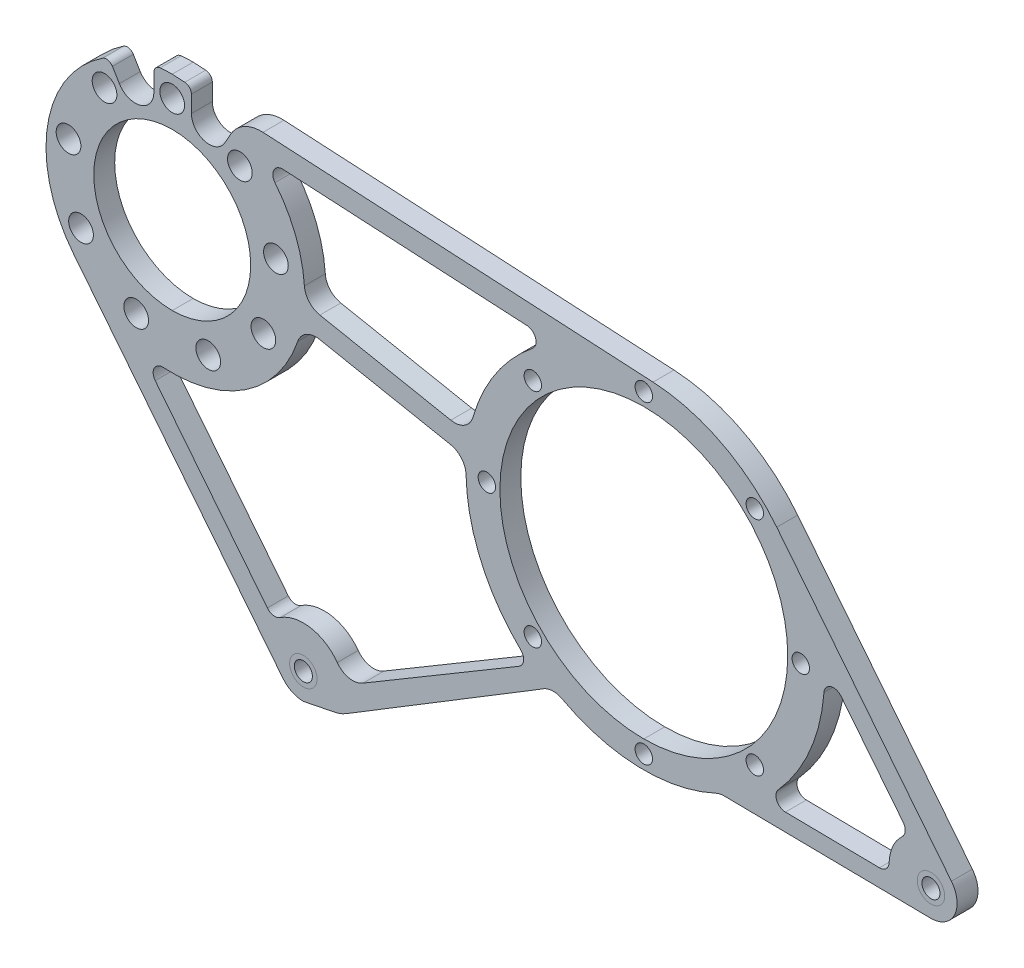
SolidWorks part; units mm, degrees
material "6061-T6 (SS)"
ref_plane "Front Plane" through (0, 0, 0) normal (0, 0, 1) x (1, 0, 0)
ref_plane "Top Plane" through (0, 0, 0) normal (0, 1, 0) x (1, 0, 0)
ref_plane "Right Plane" through (0, 0, 0) normal (1, 0, 0) x (0, 0, -1)
sketch "Sketch1" plane through (0, 0, 0) normal (0, 0, 1) x (1, 0, 0)
  line L0 (0, 0) -> (171.7726, -25.4) construction
  line L1 (47.761, -127.9853) -> (276.361, -82.1437)
  line L2 (0, 45.974) -> (175.1446, 36.4206)
  line L3 (-35.96, -28.6441) -> (40.3107, -124.3949)
  line L4 (220.1994, 13.1746) -> (283.8113, -66.6841)
  line L5 (171.7726, 36.5125) -> (171.7726, 27.0256) construction
  line L6 (0, 28.575) -> (0, 45.974) construction
  circle A0 centre (0, 0) radius 45.974
  circle A1 centre (171.7726, -25.4) radius 61.9125
  circle A2 centre (171.7726, -25.4) radius 52.4256
  circle A3 centre (0, 0) radius 28.575
  circle A4 centre (47.761, -118.4603) radius 9.525
  circle A5 centre (276.361, -72.6187) radius 9.525
  circle A6 centre (47.761, -118.4603) radius 3.2995
  circle A7 centre (276.361, -72.6187) radius 3.2995
  circle A19 centre (171.7726, -25.4) radius 57.1691 construction
  circle A21 centre (0, 0) radius 38.354 construction
  point P23 (0, 38.354)
  point P44 (0, 0)
  point P47 (171.7726, 31.7691)
  dimension "D1" = 91.948
  dimension "D2" = 123.825
  dimension "D5" = 104.8512
  dimension "D6" = 57.15
  dimension "D7" = 6.5989
  dimension "D8" = 6.5989
  dimension "D9" = 228.6
  dimension "D10" = 19.05
  dimension "D11" = 19.05
  dimension "D14" = 7.62
  dimension "D3" = 171.7726
  dimension "D4" = 25.4
  dimension "D12" = 117.2
  dimension "D13" = 76.2
extrude "Boss-Extrude1" add sketch "Sketch1" along normal blind 7.62 contours A5 L4 A1 L2 A0 L3 A4 L1 | L2 A0 A3 | A4 L1 A6 | A5 A7 | A1 A2 region at (43.7428, -126.7982, 0) region at (104.2025, -48.9688, 0) region at (268.0231, -68.6005, 0) region at (-40.2441, 19.3945, 0) region at (228.5635, -5.5459, 0)
sketch "Sketch2" plane through (0, 0, 7.62) normal (0, 0, 1) x (1, 0, 0)
  line L0 (171.7726, 36.5125) -> (171.7726, 27.0256) construction
  circle A0 centre (0, 38.354) radius 4.4996
  circle A1 centre (171.7726, 31.7691) radius 3.175
  circle A2 centre (24.6535, 29.3809) radius 4.4996
  circle A3 centre (37.7713, 6.6601) radius 4.4996
  circle A4 centre (33.2155, -19.177) radius 4.4996
  circle A5 centre (13.1178, -36.041) radius 4.4996
  circle A6 centre (-13.1178, -36.041) radius 4.4996
  circle A7 centre (-33.2155, -19.177) radius 4.4996
  circle A8 centre (-37.7713, 6.6601) radius 4.4996
  circle A9 centre (-24.6535, 29.3809) radius 4.4996
  circle A10 centre (0, 0) radius 38.354 construction
  circle A22 centre (212.1972, 15.0246) radius 3.175
  circle A23 centre (228.9416, -25.4) radius 3.175
  circle A24 centre (212.1972, -65.8246) radius 3.175
  circle A25 centre (171.7726, -82.5691) radius 3.175
  circle A26 centre (131.348, -65.8246) radius 3.175
  circle A27 centre (114.6035, -25.4) radius 3.175
  circle A28 centre (131.348, 15.0246) radius 3.175
  circle A33 centre (171.7726, -25.4) radius 57.169 construction
  point P26 (0, 0)
  point P43 (171.7726, -25.4)
  point P48 (171.7726, -25.4)
  dimension "D1" = 8.9992
  dimension "D2" = 6.35
  dimension "D3" = 9
  dimension "D4" = 8
extrude "Cut-Extrude1" cut sketch "Sketch2" against normal through all both and the other way through all
ref_plane "Plane1" through (2.54, 0, 0) normal (1, 0, 0) x (0, 0, -1)
ref_plane "Plane2" through (171.7726, 0, 0) normal (1, 0, 0) x (0, 0, -1)
split line "Split Line5"
sketch "Sketch1<4>" plane through (0, 0, 0) normal (0, 0, 1) x (1, 0, 0) same geometry as "Sketch1"
sketch "Sketch4" plane through (0, 0, 7.62) normal (0, 0, 1) x (1, 0, 0)
  circle A0 centre (276.361, -72.6187) radius 3.2995
  circle A1 centre (276.361, -72.6187) radius 5
  circle A2 centre (47.761, -118.4603) radius 3.2995
  circle A3 centre (47.761, -118.4603) radius 5
  dimension "D1" = 10
  dimension "D2" = 6.5989
split line "Split Line6"
split line "Split Line7"
split line "Split Line8"
sketch "Sketch5" plane through (0, 0, 0) normal (0, 0, -1) x (-1, 0, 0)
  line L1 (-266.229, -56.8414) -> (-243.59, -28.4202)
  line L2 (-257.604, -75.5493) -> (-223.3455, -75.1038)
  line L3 (-129.2329, 31.2936) -> (-40.3109, 36.1439)
  line L4 (-101.4745, -12.4239) -> (-53.7801, -3.115)
  line L6 (-34.6489, -105.0569) -> (6.1866, -53.7918)
  line L7 (-101.374, -20.168) -> (-53.6667, -10.8566)
  line L8 (0, 45.974) -> (-175.1446, 36.4206) construction
  line L9 (35.96, -28.6441) -> (-40.3107, -124.3949) construction
  line L11 (-220.1994, 13.1746) -> (-283.8113, -66.6841) construction
  line L12 (-171.7726, -25.4) -> (-171.7726, 974.6) construction
  line L15 (-51.4334, -127.2489) -> (-276.361, -82.1437) construction
  line L16 (-69.5282, -111.3406) -> (-126.3022, -77.645)
  line L17 (-201.074, -81.1647) -> (-276.361, -82.1437)
  line L18 (-276.361, -82.1437) -> (-61.4054, -125.2492)
  line L19 (-134.6203, -80.6651) -> (-61.4054, -125.2492)
  arc A0 (-265.8966, -61.5393) -> (-261.1275, -72.1718) centre (-276.361, -72.6187) cw
  arc A1 (-37.423, 30.4721) -> (-48.1492, 3.2677) centre (0, 0) ccw
  arc A2 (-131.222, 25.1055) -> (-109.5255, -7.4987) centre (-171.7726, -25.4) cw
  arc A3 (-61.4054, -125.2492) -> (-39.3022, -105.7833) centre (-47.761, -118.4603) cw
  arc A4 (-126.9351, -72.1414) -> (-107.0192, -26.8656) centre (-171.7726, -25.4) ccw
  arc A5 (3.2317, -48.1517) -> (-45.7124, -15.4728) centre (0, 0) cw
  arc A6 (-237.3981, -30.3277) -> (-220.7984, -69.3029) centre (-171.7726, -25.4) ccw
  arc A7 (-265.8966, -61.5393) -> (-266.229, -56.8414) centre (-263.5072, -59.0095) cw
  arc A8 (-261.1275, -72.1718) -> (-257.604, -75.5493) centre (-257.6492, -72.0697) ccw
  arc A9 (-223.3455, -75.1038) -> (-220.7984, -69.3029) centre (-223.3907, -71.6243) ccw
  arc A10 (-243.59, -28.4202) -> (-237.3981, -30.3277) centre (-240.8681, -30.5883) cw
  arc A11 (-39.3022, -105.7833) -> (-34.6489, -105.0569) centre (-37.3707, -102.8888) ccw
  arc A14 (6.1866, -53.7918) -> (3.2317, -48.1517) centre (3.4647, -51.6237) ccw
  arc A15 (-45.7124, -15.4728) -> (-53.6667, -10.8566) centre (-52.3286, -17.7123) ccw
  arc A16 (-107.0192, -26.8656) -> (-101.374, -20.168) centre (-100.036, -27.0237) cw
  arc A17 (-109.5255, -7.4987) -> (-101.4745, -12.4239) centre (-102.8126, -5.5682) ccw
  arc A18 (-48.1492, 3.2677) -> (-53.7801, -3.115) centre (-55.1182, 3.7406) cw
  arc A19 (-40.3109, 36.1439) -> (-37.423, 30.4721) centre (-40.1214, 32.6692) cw
  arc A20 (-129.2329, 31.2936) -> (-131.222, 25.1055) centre (-129.0434, 27.8189) ccw
  arc A21 (-142.131, -80.117) -> (-198.0354, -81.8167) centre (-171.7726, -25.4) cw
  arc A22 (-126.3022, -77.645) -> (-126.9351, -72.1414) centre (-124.5262, -74.6526) cw
  arc A23 (-198.0354, -81.8167) -> (-201.074, -81.1647) centre (-200.9832, -88.1491) ccw
  arc A24 (-134.6203, -80.6651) -> (-142.131, -80.117) centre (-138.8038, -86.2587) ccw
  arc A25 (-69.5282, -111.3406) -> (-60.1156, -109.5373) centre (-65.7782, -105.4476) ccw
  point P41 (-268.4302, -59.6048)
  point P44 (-291.2242, -75.9864)
  point P47 (-215.0307, -74.9957)
  point P50 (-237.4123, -20.6647)
  point P80 (-47.293, -9.6126)
  point P83 (-107.133, -21.292)
  line M26 (-276.361, -82.1437) -> (-51.4334, -127.2489)
  dimension "D1" = 15.24
  dimension "D7" = 3.4798
  dimension "D8" = 15.24
  dimension "D11" = 64.77
  dimension "D13" = 64.77
  dimension "D14" = 48.26
  dimension "D15" = 3.4798
  dimension "D16" = 48.26
  dimension "D17" = 7.62
  dimension "D18" = 6.985
  dimension "D19" = 3.4798
  dimension "D20" = 0.65
  dimension "D10" = 3.4798
  dimension "D23" = 6.985
  dimension "D24" = 6.985
  dimension "D26" = 6.985
  dimension "D29" = 66.0203
  dimension "D30" = 86.632
  dimension "D31" = 62.23
  dimension "D2" = 49.784
  dimension "D3" = 76.2
  dimension "D4" = 7.62
  dimension "D5" = 6.35
  dimension "D9" = 7.62
  dimension "D12" = 7.62
  dimension "D25" = 20
  dimension "D27" = 85.7214
  dimension "D28" = 0
extrude "Cut-Extrude2" cut sketch "Sketch5" against normal through all both and the other way through all contours L16 A25 A3 A11 L6 A14 A5 A15 L7 A16 A4 A22 | L19 A24 A21 A23 L17 M26 | L3 A20 A2 A17 L4 A18 A1 A19 | A10 L1 A7 A0 A8 L2 A9 A6 region at (244.5472, -57.2693, 0) region at (83.052, 14.7275, 0) region at (64.0038, -61.6283, 0) region at (156.4454, -96.96, 0)
fillet "Fillet2" radius 12.7 1 edges at (61.4054, -125.2492, 3.81)
sketch "Sketch6" plane through (0, 0, 0) normal (0, 0, -1) x (-1, 0, 0)
  line L0 (-19.1496, 33.8712) -> (-24.6535, 29.3809) construction
  line L1 (-6.9836, 37.0561) -> (0, 38.354) construction
  line L2 (-19.1496, 33.8712) -> (-25.1805, 44.6005)
  line L3 (-5.0005, 45.7012) -> (-175.1446, 36.4206) construction
  line L4 (-6.9836, 37.0561) -> (-6.9836, 45.5931)
  line L5 (6.6943, 36.8702) -> (6.6943, 45.484)
  line L6 (19.2601, 33.3713) -> (23.1077, 39.7447)
  line L7 (-25.1805, 44.6005) -> (-6.9836, 45.5931)
  arc A0 (-6.9836, 37.0561) -> (-19.1496, 33.8712) centre (-13.4835, 37.0561) cw
  arc A1 (6.6943, 36.8702) -> (19.2601, 33.3713) centre (13.4643, 36.8702) ccw
  arc A2 (35.96, -28.6441) -> (0, 45.974) centre (0, 0) ccw construction
  arc A3 (6.6943, 45.484) -> (23.1077, 39.7447) centre (0, 0) cw
  point P5 (-11.8374, 30.7681)
  point P12 (11.6483, 30.3483)
  dimension "D1" = 6.4999
  dimension "D2" = 32.9667
  dimension "D3" = 32.5069
  dimension "D4" = 13.5458
  dimension "D5" = 13.5458
  dimension "D6" = 13.6779
  dimension "D7" = 7.4447
extrude "Cut-Extrude3" cut sketch "Sketch6" against normal through all both and the other way through all
fillet "Fillet3" radius 2.54 3 edges at (-6.6943, 45.484, 3.81) (-23.1077, 39.7447, 3.81)
fillet "Fillet4" radius 12.7 1 edges at (25.1805, 44.6005, 3.81)
